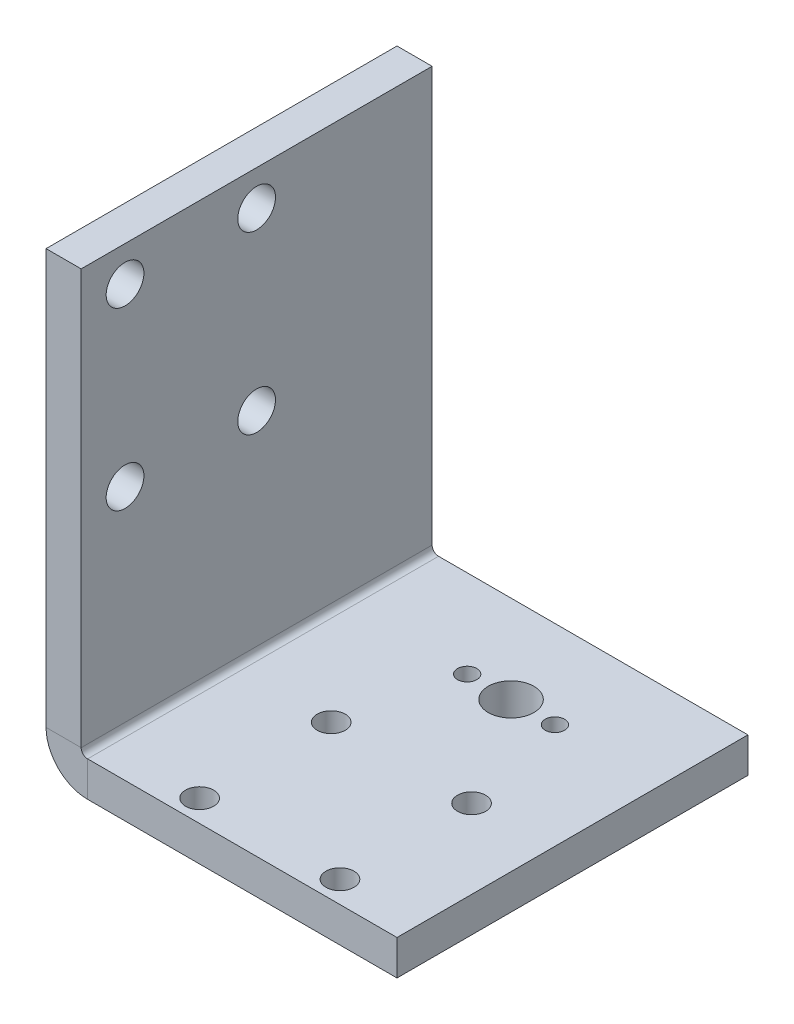
SolidWorks part; units mm, degrees
note: The reader was unsure of these and kept them because the rebuilt part matched: thickness of "基材-凸緣2", "鈑金4", "鈑金5", "鈑金6", "鈑金7", "鈑金8", "鈑金9"; bend radius of "基材彎折1".
material "AISI 304"
ref_plane "前基準面" through (0, 0, 0) normal (0, 0, 1) x (1, 0, 0)
ref_plane "上基準面" through (0, 0, 0) normal (0, 1, 0) x (1, 0, 0)
ref_plane "右基準面" through (0, 0, 0) normal (1, 0, 0) x (0, 0, -1)
sketch "草圖16" plane through (0, 0, 0) normal (0, 0, 1) x (1, 0, 0)
  line L0 (0, 0) -> (0, 48)
  line L1 (0, 0) -> (36, 0)
  dimension "D1" = 36
  dimension "D2" = 48
base flange "基材-凸緣2" sketch "草圖16" end condition mid plane depth 40 reverse direction no thickness 4 reverse thickness direction no bend radius 0.7366
bend "基材彎折1" bend radius 0.7366 bend angle 90 parameters "D5"=1
sketch "草圖21" plane through (-4, 0, 0) normal (-1, 0, 0) x (0, 0, 1)
  line L0 (20, 0) -> (-20, 0) construction
  line L1 (2, 0.7366) -> (15.5, 0.7366)
  line L2 (2, 0.7366) -> (2, 22)
  line L3 (2, 22) -> (15.5, 22)
  line L4 (15.5, 0.7366) -> (15.5, 22)
  line L5 (2, 0.7366) -> (15.5, 22) construction
  line L6 (2, 22) -> (15.5, 0.7366) construction
  line L7 (-20, 48) -> (-20, 0.7366) construction
  line L9 (20, 0.7366) -> (-20, 0.7366) construction
  point P4 (8.75, 11.3683)
  dimension "D1" = 22
  dimension "D2" = 13.5
  dimension "D3" = 22
extrude "除料-伸長1" [suppressed] cut sketch "草圖21" against normal blind 20
hole_wizard "M3 餘隙孔1" positions "草圖22" profile "草圖23" hole size "M3" standard "Ansi Metric" end condition through all
sketch "草圖22" plane through (0, 0, 0) normal (0, -1, 0) x (-1, 0, 0)
  line L1 (-11, -2.5) -> (-27, -2.5) construction
  line L2 (-11, -2.5) -> (-11, -17.5) construction
  line L3 (-11, -17.5) -> (-27, -17.5) construction
  line L4 (-27, -2.5) -> (-27, -17.5) construction
  line L5 (-11, -2.5) -> (-27, -17.5) construction
  line L6 (-11, -17.5) -> (-27, -2.5) construction
  line L11 (4, -20) -> (4, 20) construction
  line L13 (-0.7366, -20) -> (-36, -20) construction
  point P2 (-27, -17.5)
  point P57 (-11, -2.5)
  point P58 (-11, -17.5)
  point P59 (-27, -2.5)
  point P95 (-19, -10)
  dimension "D1" = 16
  dimension "D2" = 15
  dimension "D3" = 10
  dimension "D4" = 15
sketch "草圖23" plane through (27, 0, 17.5) normal (1, 0, 0) x (0, 0, 1)
  line L0 (0, 0) -> (0, 4)
  line L1 (0, 4) -> (1.6, 4)
  line L2 (1.6, 4) -> (1.6, 0)
  line L5 (1.6, 0) -> (0, 0)
  line L11 (0, -6.35) -> (0, 107.95) construction
  dimension "砮 ふ 畖" = 3.2
  dimension "砮 ふ瞏 " = 4
sketch "草圖24" plane through (0, -4, 0) normal (0, -1, 0) x (1, 0, 0)
  line L0 (19, 10) -> (19, -10) construction
  line L1 (11, 17.5) -> (27, 17.5) construction
  line L2 (11, 17.5) -> (11, 2.5) construction
  line L3 (11, 2.5) -> (27, 2.5) construction
  line L4 (27, 17.5) -> (27, 2.5) construction
  line L5 (11, 17.5) -> (27, 2.5) construction
  line L6 (11, 2.5) -> (27, 17.5) construction
  circle A0 centre (19, -10) radius 2.6
  point P4 (19, 10)
  point P13 (19, -10)
  dimension "D1" = 5.2
  dimension "D2" = 20
extrude "除料-伸長2" cut sketch "草圖24" against normal through all normal cut yes
hole_wizard "M4 餘隙孔1" positions "草圖27" profile "草圖28" hole size "M4" standard "Ansi Metric" end condition through all
sketch "草圖27" plane through (0, 0, 0) normal (-1, 0, 0) x (0, 0, 1)
  line L1 (15, 44) -> (-15, 44) construction
  line L2 (15, 44) -> (15, 24) construction
  line L3 (15, 24) -> (-15, 24) construction
  line L4 (-15, 44) -> (-15, 24) construction
  line L5 (15, 44) -> (-15, 24) construction
  line L6 (15, 24) -> (-15, 44) construction
  line L7 (0, 0) -> (0, 34) construction
  line L10 (20, 48) -> (-20, 48) construction
  point P104 (15, 44)
  point P105 (15, 24)
  point P133 (0, 24)
  point P135 (0, 44)
  dimension "D1" = 30
  dimension "D2" = 20
  dimension "D3" = 14
sketch "草圖28" plane through (0, 44, 0) normal (0, 1, 0) x (0, 0, -1)
  line L0 (0, 0) -> (0, 4)
  line L1 (0, 4) -> (2.15, 4)
  line L2 (2.15, 4) -> (2.15, 0)
  line L5 (2.15, 0) -> (0, 0)
  line L11 (0, -6.35) -> (0, 107.95) construction
  dimension "砮 ふ 畖" = 4.3
  dimension "砮 ふ瞏 " = 4
hole_wizard "M2 餘隙孔1" positions "草圖25" profile "草圖26" hole size "M2" standard "Ansi Metric" end condition through all
sketch "草圖25" plane through (0, -4, 0) normal (0, -1, 0) x (-1, 0, 0)
  line L0 (-14, 10) -> (-24, 10) construction
  circle A0 centre (-19, 10) radius 2.6 construction
  point P0 (-14, 10)
  point P1 (-24, 10)
  point P4 (-19, 10)
  dimension "D1" = 10
sketch "草圖26" plane through (14, -4, -10) normal (1, 0, 0) x (0, 0, -1)
  line L0 (0, 0) -> (0, 52)
  line L1 (0, 52) -> (1.1, 52)
  line L2 (1.1, 52) -> (1.1, 0)
  line L5 (1.1, 0) -> (0, 0)
  line L11 (0, -6.35) -> (0, 107.95) construction
  dimension "砮 ふ 畖" = 2.2
  dimension "砮 ふ瞏 " = 52
sketch "彎折-線3" [suppressed] plane through (0, 0, 0) normal (0, 1, 0) x (1, 0, 0)
sketch "邊界方塊3" [suppressed] plane through (0, 0, 0) normal (0, 1, 0) x (1, 0, 0)
sheet metal parameters "鈑金4" thickness 4 parameters "D1"=0.7366
flat pattern "平板-型式4" [suppressed]
sketch "彎折-線4" plane through (0, 0, 0) normal (0, 1, 0) x (1, 0, 0)
  line L0 (-1.4127, -20) -> (-1.4127, 20) construction
  line L1 (-1.4127, -20) -> (-1.4127, 20) construction
sketch3d "邊界方塊4" [suppressed]
  line L0 (60, 0, 0) -> (-32.8254, 0, 0) construction
  line L1 (60, 40, 0) -> (-32.8254, 40, 0) construction
  line L2 (60, 0, 0) -> (60, 40, 0) construction
  line L3 (-32.8254, 0, 0) -> (-32.8254, 40, 0) construction
bend of the flat pattern "平板-<基材彎折1>1"
sheet metal parameters "鈑金5" thickness 4 parameters "D1"=0.7366
flat pattern "平板-型式4"
sketch "彎折-線4" plane through (0, 0, 0) normal (0, 1, 0) x (1, 0, 0)
  line L0 (-1.4127, -20) -> (-1.4127, -14) construction
  line L1 (-1.4127, -20) -> (-1.4127, -14) construction
  line L2 (-1.4127, 1) -> (-1.4127, 20) construction
sketch3d "邊界方塊4" [suppressed]
  line L0 (60, 0, 0) -> (-42.8254, 0, 0) construction
  line L1 (60, 40, 0) -> (-42.8254, 40, 0) construction
  line L2 (60, 0, 0) -> (60, 40, 0) construction
  line L3 (-42.8254, 0, 0) -> (-42.8254, 40, 0) construction
bend of the flat pattern "平板-<基材彎折1>1"
sheet metal parameters "鈑金6" thickness 4 parameters "D1"=0.7366
flat pattern "平板-型式4"
sketch "彎折-線4" plane through (0, 0, 0) normal (0, 1, 0) x (1, 0, 0)
  line L0 (-1.4127, -20) -> (-1.4127, 20) construction
  line L1 (-1.4127, -20) -> (-1.4127, 20) construction
sketch3d "邊界方塊4" [suppressed]
  line L0 (40, 0, 0) -> (-42.8254, 0, 0) construction
  line L1 (40, 40, 0) -> (-42.8254, 40, 0) construction
  line L2 (40, 0, 0) -> (40, 40, 0) construction
  line L3 (-42.8254, 0, 0) -> (-42.8254, 40, 0) construction
bend of the flat pattern "平板-<基材彎折1>1"
sheet metal parameters "鈑金7" thickness 4 parameters "D1"=0.7366
flat pattern "平板-型式4"
sketch "彎折-線4" plane through (0, 0, 0) normal (0, 1, 0) x (1, 0, 0)
  line L0 (-1.4127, -20) -> (-1.4127, 20) construction
  line L1 (-1.4127, -20) -> (-1.4127, 20) construction
sketch3d "邊界方塊4" [suppressed]
  line L0 (40, 0, 0) -> (-42.8254, 0, 0) construction
  line L1 (40, 40, 0) -> (-42.8254, 40, 0) construction
  line L2 (40, 0, 0) -> (40, 40, 0) construction
  line L3 (-42.8254, 0, 0) -> (-42.8254, 40, 0) construction
bend of the flat pattern "平板-<基材彎折1>1"
sheet metal parameters "鈑金8" thickness 4 parameters "D1"=0.7366
flat pattern "平板-型式4"
sketch "彎折-線4" plane through (0, 0, 0) normal (0, 1, 0) x (1, 0, 0)
  line L0 (-1.4127, -20) -> (-1.4127, 20) construction
  line L1 (-1.4127, -20) -> (-1.4127, 20) construction
sketch3d "邊界方塊4" [suppressed]
  line L0 (36, 0, 0) -> (-50.8254, 0, 0) construction
  line L1 (36, 40, 0) -> (-50.8254, 40, 0) construction
  line L2 (36, 0, 0) -> (36, 40, 0) construction
  line L3 (-50.8254, 0, 0) -> (-50.8254, 40, 0) construction
bend of the flat pattern "平板-<基材彎折1>1"
sheet metal parameters "鈑金9" thickness 4 parameters "D1"=0.7366
flat pattern "平板-型式4"
sketch "彎折-線4" plane through (0, 0, 0) normal (0, 1, 0) x (1, 0, 0)
  line L0 (-1.02, -30) -> (-1.02, 30) construction
  line L1 (-1.02, -30) -> (-1.02, 30) construction
sketch3d "邊界方塊4" [suppressed]
  line L0 (40, 0, 0) -> (-52.04, 0, 0) construction
  line L1 (40, 60, 0) -> (-52.04, 60, 0) construction
  line L2 (40, 0, 0) -> (40, 60, 0) construction
  line L3 (-52.04, 0, 0) -> (-52.04, 60, 0) construction
bend of the flat pattern "平板-<基材彎折1>1"
